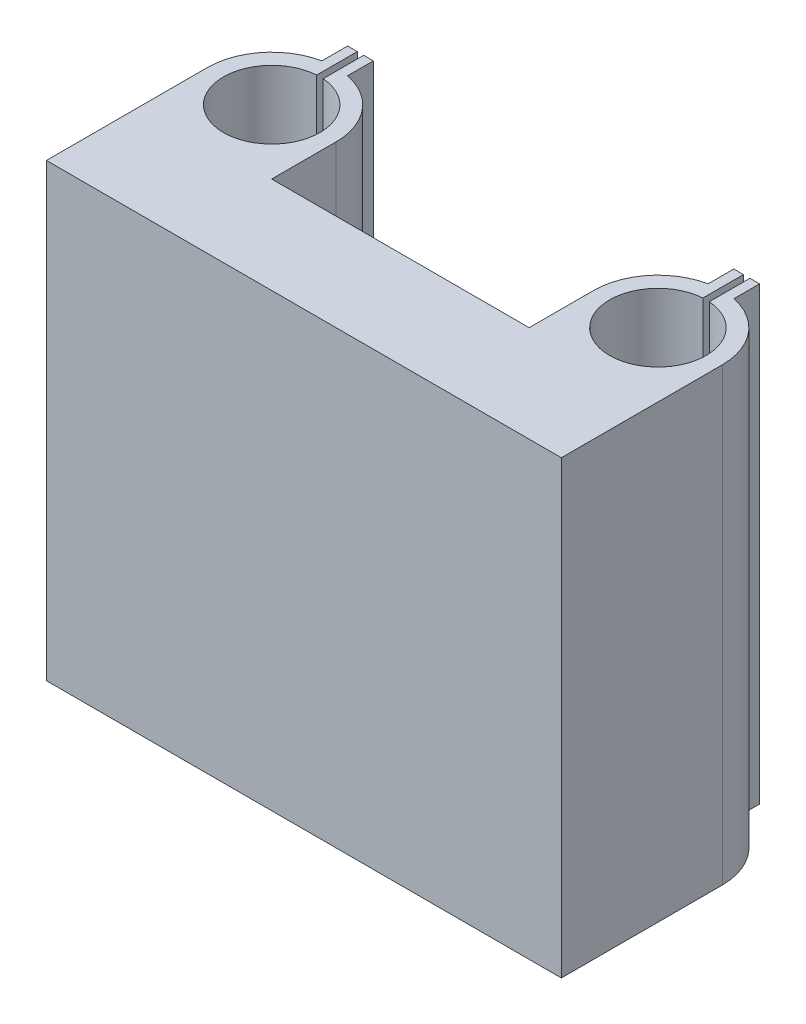
SolidWorks part; units mm, degrees
ref_plane "Alzado" through (0, 0, 0) normal (0, 0, 1) x (1, 0, 0)
ref_plane "Planta" through (0, 0, 0) normal (0, 1, 0) x (1, 0, 0)
ref_plane "Vista lateral" through (0, 0, 0) normal (1, 0, 0) x (0, 0, -1)
sketch "Croquis1" plane through (0, 0, 0) normal (0, 1, 0) x (1, 0, 0)
  line L0 (-58.0166, 0) -> (58.0166, 0) construction
  line L5 (40, -25) -> (40, 0)
  line L6 (11.3137, 4) -> (20.8348, 4)
  line L7 (0, 33.1459) -> (0, -45.5761) construction
  line L8 (-40, -25) -> (-40, 0)
  line L9 (-11.3137, 4) -> (-20.8348, 4)
  line L10 (-40, -25) -> (40, -25)
  arc A1 (11.3137, 4) -> (-11.3137, 4) centre (0, 0) ccw
  arc A2 (40, 0) -> (20.8348, 4) centre (30, 0) ccw
  arc A3 (-40, 0) -> (-20.8348, 4) centre (-30, 0) cw
  point P3 (0, 0)
  dimension "D1" = 20
  dimension "D2" = 24
  dimension "D3" = 30
  dimension "D4" = 4
  dimension "D5" = 25
extrude "Saliente-Extruir1" add sketch "Croquis1" along normal blind 70
sketch "Croquis3" plane through (0, 70, 0) normal (0, 1, 0) x (1, 0, 0)
  line L0 (-30, 0) -> (-30, 16.5211) construction
  line L1 (-32, 9.798) -> (-32, 13.798)
  line L2 (-32, 13.798) -> (-28, 13.798)
  line L3 (-28, 9.798) -> (-28, 13.798)
  line L4 (0, -55) -> (0, 55) construction
  line L5 (28, 9.798) -> (28, 13.798)
  line L6 (32, 13.798) -> (28, 13.798)
  line L7 (32, 9.798) -> (32, 13.798)
  arc A0 (-20.8348, 4) -> (-40, 0) centre (-30, 0) ccw construction
  arc A1 (-28, 9.798) -> (-32, 9.798) centre (-30, 0) ccw
  arc A2 (28, 9.798) -> (32, 9.798) centre (30, 0) cw
  point P10 (-30, 13.798)
  dimension "D1" = 4
  dimension "D2" = 4
extrude "Saliente-Extruir2" add sketch "Croquis3" against normal up to surface (70 mm away) up to face at (0, 0, 1.3027)
sketch "Croquis4" plane through (0, 70, 0) normal (0, 1, 0) x (1, 0, 0)
  line L0 (-30.5, 7.4833) -> (-30.5, 14.6548)
  line L1 (-30, 0) -> (-30, 16.6168) construction
  line L2 (-30.5, 14.6548) -> (-29.5, 14.6548)
  line L3 (-29.5, 7.4833) -> (-29.5, 14.6548)
  line L4 (0, -55) -> (0, 55) construction
  line L5 (29.5, 7.4833) -> (29.5, 14.6548)
  line L6 (30.5, 14.6548) -> (29.5, 14.6548)
  line L7 (30.5, 7.4833) -> (30.5, 14.6548)
  arc A1 (-30.5, 7.4833) -> (-29.5, 7.4833) centre (-30, 0) ccw
  arc A2 (30.5, 7.4833) -> (29.5, 7.4833) centre (30, 0) cw
  point P8 (-30, 14.6548)
  point P16 (30, 14.6548)
  dimension "D1" = 15
  dimension "D2" = 1
extrude "Cortar-Extruir2" cut sketch "Croquis4" against normal through all both and the other way through all
sketch "Croquis5" plane through (0, 70, 0) normal (0, 1, 0) x (1, 0, 0)
  line L0 (-20, 0) -> (-20, -10)
  line L1 (-20, -10) -> (20, -10)
  line L2 (0, 31.6012) -> (0, -31.6012) construction
  line L3 (-20, -10) -> (-30, -10) construction
  line L7 (20, 0) -> (20, -10)
  line L8 (-20.8348, 4) -> (-20.8348, 13.996)
  line L9 (-20.8348, 13.996) -> (20.8348, 13.996)
  line L10 (20.8348, 13.996) -> (20.8348, 4)
  arc A0 (11.3137, 4) -> (-11.3137, 4) centre (0, 0) ccw construction
  arc A3 (-32, 9.798) -> (-40, 0) centre (-30, 0) ccw construction
  arc A4 (-32, 9.798) -> (-40, 0) centre (-30, 0) ccw construction
  arc A5 (-20, 0) -> (-20.8348, 4) centre (-30, 0) ccw
  arc A6 (-32, 9.798) -> (-40, 0) centre (-30, 0) ccw construction
  arc A7 (20, 0) -> (20.8348, 4) centre (30, 0) cw
  point P9 (0, 0)
  point P16 (0, -10)
extrude "Cortar-Extruir3" cut sketch "Croquis5" against normal offset from surface 10 and the other way through all up to face at (0, 0, -5.3393)
sketch "Croquis6" plane through (0, 70, 0) normal (0, 1, 0) x (1, 0, 0)
  line L0 (0, 0) -> (-12.9386, 12.9386) construction
  line L1 (0, 0) -> (0, 16.0434) construction
  circle A0 centre (0, 0) radius 5
  circle A1 centre (-6.0104, 6.0104) radius 1.6
  circle A2 centre (6.0104, 6.0104) radius 1.6
  circle A3 centre (6.0104, -6.0104) radius 1.6
  circle A4 centre (-6.0104, -6.0104) radius 1.6
  point P7 (-9.117, -6.9131)
  point P8 (0, 0)
  point P16 (0, 0)
  dimension "D1" = 10
  dimension "D3" = 3.2
  dimension "D4" = 8.5
  dimension "D2" = 45
  dimension "D5" = 4
extrude "Cortar-Extruir4" cut sketch "Croquis6" against normal through all both and the other way through all
